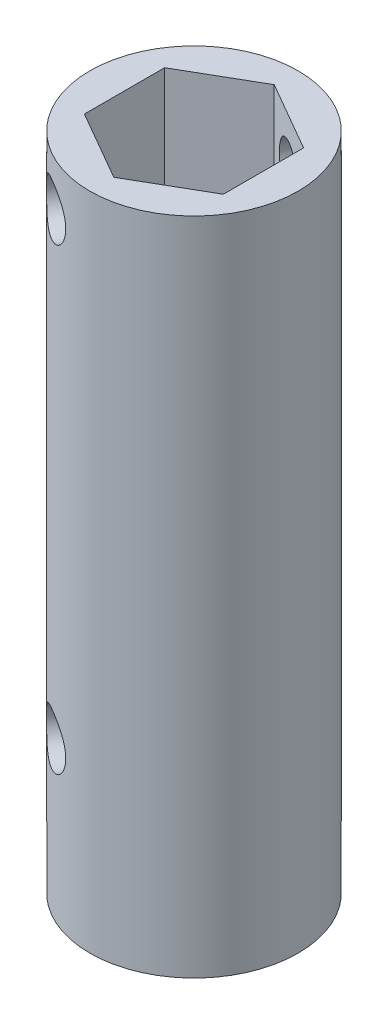
SolidWorks part; units mm, degrees
ref_plane "Front" through (0, 0, 0) normal (0, 0, 1) x (1, 0, 0)
ref_plane "Top" through (0, 0, 0) normal (0, 1, 0) x (1, 0, 0)
ref_plane "Right" through (0, 0, 0) normal (1, 0, 0) x (0, 0, -1)
sketch "Sketch1" plane through (0, 0, 0) normal (0, 1, 0) x (1, 0, 0)
  line L1 (0, 7.3323) -> (-6.35, 3.6662)
  line L2 (-6.35, 3.6662) -> (-6.35, -3.6662)
  line L3 (-6.35, -3.6662) -> (0, -7.3323)
  line L4 (0, -7.3323) -> (6.35, -3.6662)
  line L5 (6.35, -3.6662) -> (6.35, 3.6662)
  line L6 (6.35, 3.6662) -> (0, 7.3323)
  circle A0 centre (0, 0) radius 6.35 construction
  circle A1 centre (0, 0) radius 9.525
  dimension "D2" = 19.05
  dimension "D1" = 12.7
extrude "Boss-Extrude1" add sketch "Sketch1" along normal blind 60.325
ref_plane "Plane1" through (-5.08, 0, 8.7988) normal (0.5, 0, -0.866) x (-0.866, 0, -0.5)
sketch "Sketch2" plane through (-5.08, 0, 8.7988) normal (0.5, 0, -0.866) x (-0.866, 0, -0.5)
  line L0 (-9.525, 0) -> (9.525, 0) construction
  line L1 (9.525, 60.325) -> (-9.525, 60.325) construction
  line L3 (0, 55.88) -> (0, 0) construction
  circle A0 centre (0, 55.88) radius 2.3812
  circle A1 centre (0, 13.97) radius 2.3813
  point P8 (0, -2.5267)
  point P11 (0, 0)
  dimension "D3" = 4.7625
  dimension "D1" = 13.97
  dimension "D2" = 4.445
extrude "Cut-Extrude1" cut sketch "Sketch2" against normal through all both and the other way through all
